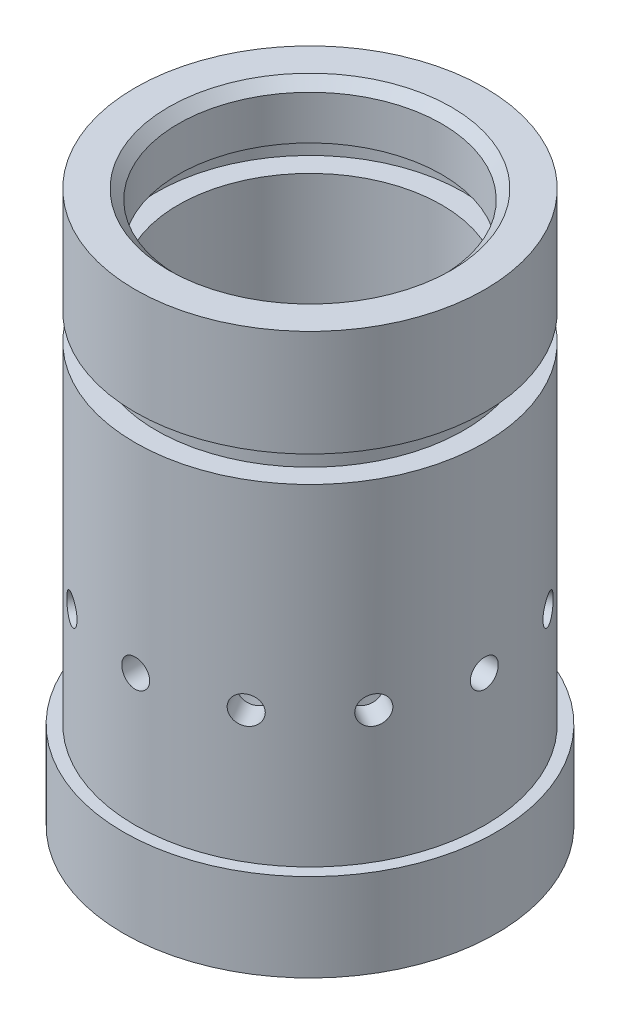
SolidWorks part; units mm, degrees
material "6061 Alloy"
ref_plane "Front Plane" through (0, 0, 0) normal (0, 0, 1) x (1, 0, 0)
ref_plane "Top Plane" through (0, 0, 0) normal (0, 1, 0) x (1, 0, 0)
ref_plane "Right Plane" through (0, 0, 0) normal (1, 0, 0) x (0, 0, -1)
sketch "Sketch1" plane through (0, 0, 0) normal (0, 0, 1) x (1, 0, 0)
  line L0 (0, 0) -> (0, 10.9165) construction
  line L1 (19.05, -57.6721) -> (19.05, -16.0161)
  line L2 (19.05, -16.0161) -> (20.447, -14.6191)
  line L3 (20.447, -14.6191) -> (25.2857, -14.6191)
  line L6 (25.2857, -14.6191) -> (25.2857, -57.6721)
  line L7 (25.2857, -57.6721) -> (19.05, -57.6721)
  line L8 (19.05, -57.6721) -> (15.875, -57.6721)
  line L9 (15.875, -57.6721) -> (25.7175, -94.4048)
  line L11 (25.7175, -94.4048) -> (26.9875, -94.4048)
  line L13 (15.875, -57.6721) -> (7.9375, -28.0489) construction
  line L14 (26.9875, -81.7048) -> (26.9875, -94.4048)
  line L15 (25.2857, -57.6721) -> (25.2857, -81.7048)
  line L16 (-26.9875, -81.7048) -> (26.9875, -81.7048) construction
  line L17 (25.2857, -81.7048) -> (26.9875, -81.7048)
  line L18 (-26.9875, -81.7048) -> (-26.9875, -94.4048)
  line L19 (-26.9875, -94.4048) -> (26.9875, -94.4048) construction
  line L20 (-22.2123, -14.6191) -> (22.2123, -14.6191) construction
  line L21 (19.05, -22.3661) -> (22.225, -22.3661)
  line L22 (25.2857, -29.9861) -> (22.225, -29.9861)
  line L23 (25.2857, -29.9861) -> (25.2857, -33.7961)
  line L24 (25.2857, -33.7961) -> (22.225, -33.7961)
  line L25 (22.225, -29.9861) -> (22.225, -33.7961)
  line L26 (19.05, -22.3661) -> (19.05, -26.1761)
  line L27 (19.05, -26.1761) -> (22.225, -26.1761)
  line L28 (22.225, -22.3661) -> (22.225, -26.1761)
  line L29 (-25.7175, -94.4048) -> (-26.9875, -94.4048)
  line L30 (-15.875, -57.6721) -> (-25.7175, -94.4048)
  line L31 (-22.225, -22.3661) -> (-22.225, -26.1761)
  line L32 (-19.05, -26.1761) -> (-22.225, -26.1761)
  line L33 (-19.05, -22.3661) -> (-19.05, -26.1761)
  line L34 (-22.225, -29.9861) -> (-22.225, -33.7961)
  line L35 (-25.2857, -33.7961) -> (-22.225, -33.7961)
  line L36 (-25.2857, -29.9861) -> (-25.2857, -33.7961)
  line L37 (-25.2857, -29.9861) -> (-22.225, -29.9861)
  line L38 (-19.05, -22.3661) -> (-22.225, -22.3661)
  line L39 (-25.2857, -81.7048) -> (-26.9875, -81.7048)
  line L40 (-25.2857, -57.6721) -> (-25.2857, -81.7048)
  line L41 (-19.05, -57.6721) -> (-15.875, -57.6721)
  line L42 (-25.2857, -57.6721) -> (-19.05, -57.6721)
  line L43 (-25.2857, -14.6191) -> (-25.2857, -57.6721)
  line L44 (-20.447, -14.6191) -> (-25.2857, -14.6191)
  line L45 (-19.05, -16.0161) -> (-20.447, -14.6191)
  line L46 (-19.05, -57.6721) -> (-19.05, -16.0161)
  point P26 (25.2857, -14.6191)
  point P37 (15.875, -57.6721)
  point P53 (-15.875, -57.6721)
  point P54 (-25.2857, -14.6191)
  dimension "D1" = 44.45
  dimension "D2" = 3.81
  dimension "D3" = 44.45
  dimension "D4" = 3.81
  dimension "D5" = 19.05
  dimension "D6" = 45
  dimension "D7" = 1.397
  dimension "D8" = 3.0607
  dimension "D9" = 6.35
revolve "Revolve1" add sketch "Sketch1" angle 360 about L0 region at (22.1785, -37.0228, 0) region at (22.6048, -71.4974, 0)
ref_plane "Plane1" through (0, 0, -25.2857) normal (0, 0, -1) x (-1, 0, 0)
sketch "Sketch2" plane through (0, 0, -25.2857) normal (0, 0, -1) x (-1, 0, 0)
  point P0 (0, -62.6548)
hole_wizard "#10-32 Tapped Hole1" positions "Sketch2" profile "Sketch3" tap size "#10-32" standard "ANSI Inch"
sketch "Sketch3" plane through (0, -62.6548, -25.2857) normal (1, 0, 0) x (0, 1, 0)
  line L0 (0, 0) -> (0, 4.1661)
  line L1 (0, 4.1661) -> (2.0193, 3.81)
  line L2 (2.0193, 3.81) -> (2.0193, 0)
  line L5 (2.0193, 0) -> (0, 0)
  line L10 (0, 4.1661) -> (-2.0193, 3.81) construction
  line L11 (0, -6.35) -> (0, 107.95) construction
  dimension "Tap Drill Dia." = 4.0386
  dimension "Tap Drill Depth" = 3.81
  dimension "Drill Angle" = 160
pattern_circular "CirPattern1" count 12 over 360 about axis through (0, 0, 0) along (0, -1, 0) of "#10-32 Tapped Hole1" reverse direction yes
